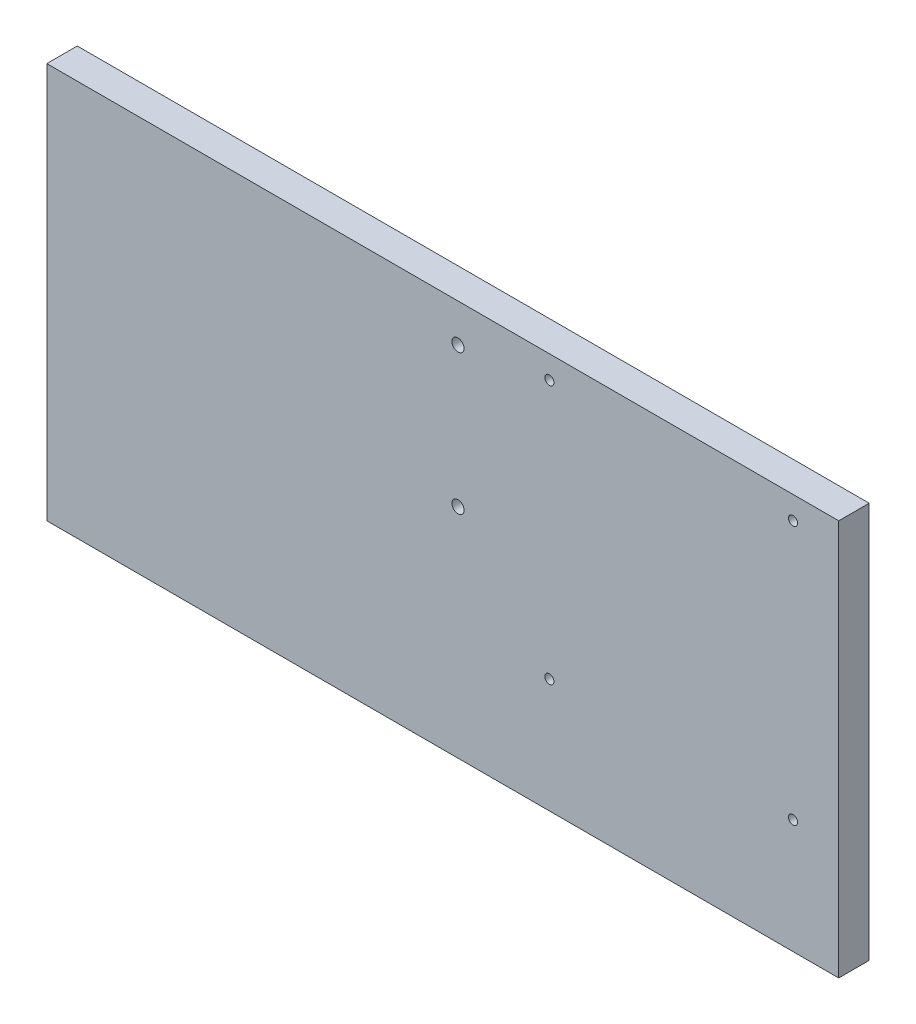
SolidWorks part; units mm, degrees
material "Faia"
ref_plane "Plano frontal" through (0, 0, 0) normal (0, 0, 1) x (1, 0, 0)
ref_plane "Plano superior" through (0, 0, 0) normal (0, 1, 0) x (1, 0, 0)
ref_plane "Plano direito" through (0, 0, 0) normal (1, 0, 0) x (0, 0, -1)
sketch "Esboço1" plane through (0, 0, 0) normal (0, 0, 1) x (1, 0, 0)
  line L0 (130, 0) -> (-130, 0) construction
  line L1 (-130, 65) -> (130, 65)
  line L2 (-130, 65) -> (-130, -65)
  line L3 (-130, -65) -> (130, -65)
  line L4 (130, 65) -> (130, -65)
  line L5 (-130, 65) -> (130, -65) construction
  line L6 (-130, -65) -> (130, 65) construction
  line L7 (50, 0) -> (-210, 0) construction
  line L8 (5, 6.5) -> (5, 52.5) construction
  circle A0 centre (115, 57.5) radius 1.5
  circle A1 centre (115, -27.5) radius 1.5
  circle A2 centre (35, -27.5) radius 1.5
  circle A3 centre (35, 57.5) radius 1.5
  circle A4 centre (5, 52.5) radius 2
  circle A5 centre (5, 6.5) radius 2
  point P0 (0, 0)
  point P21 (5, 0)
  point P23 (115, 42.5)
  point P24 (0, 0)
  point P25 (0, 0)
  point P26 (0, 0)
  point P27 (115, 42.5)
  point P28 (115, 52.285)
  dimension "D5" = 3
  dimension "D8" = 4
  dimension "D1" = 260
  dimension "D2" = 130
  dimension "D3" = 15
  dimension "D4" = 85
  dimension "D7" = 80
  dimension "D9" = 46
  dimension "D10" = 125
  dimension "D11" = 12.5
  dimension "D12" = 7.5
  dimension "D6" = 2
extrude "Ressalto-extrusão1" add sketch "Esboço1" along normal blind 10 contours L4 L1 L2 L3 A3 A1 A0 A2 region at (-0.0666, -0.0345, 0)
